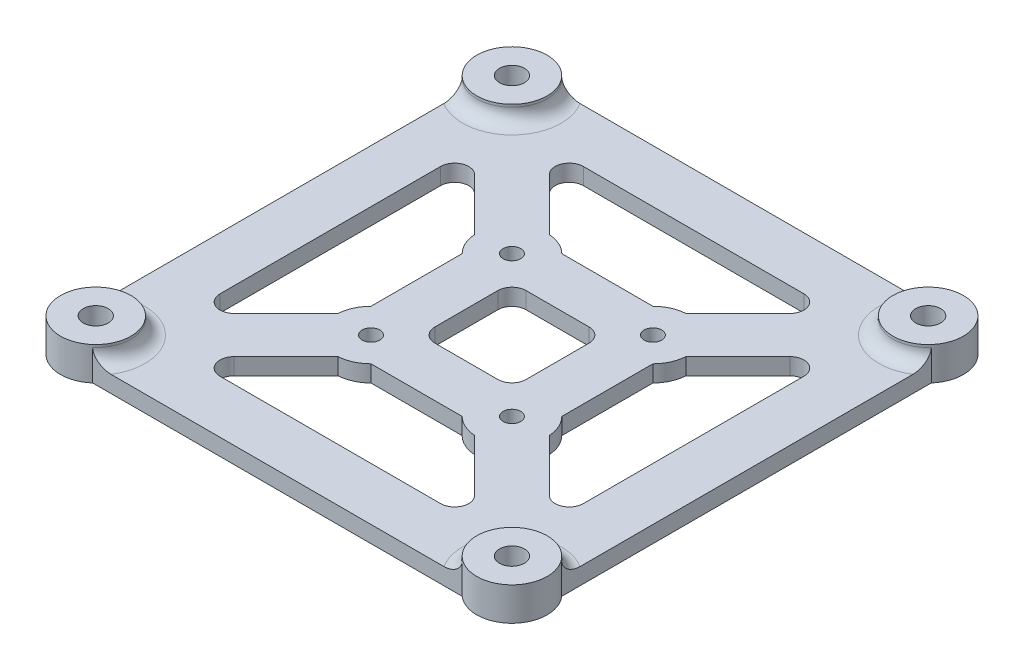
SolidWorks part; units mm, degrees
ref_plane "Front Plane" through (0, 0, 0) normal (0, 0, 1) x (1, 0, 0)
ref_plane "Top Plane" through (0, 0, 0) normal (0, 1, 0) x (1, 0, 0)
ref_plane "Right Plane" through (0, 0, 0) normal (1, 0, 0) x (0, 0, -1)
sketch "Sketch1" plane through (0, 0, 0) normal (0, 1, 0) x (1, 0, 0)
  line L0 (-26.0023, -32.7375) -> (-12.3023, -19.0375)
  line L1 (-12.7, -12.7) -> (12.7, -12.7) construction
  line L2 (-12.7, -12.7) -> (-12.7, 12.7) construction
  line L3 (-12.7, 12.7) -> (12.7, 12.7) construction
  line L4 (12.7, -12.7) -> (12.7, 12.7) construction
  line L5 (-12.7, -12.7) -> (12.7, 12.7) construction
  line L6 (-12.7, 12.7) -> (12.7, -12.7) construction
  line L7 (-37.5, -37.5) -> (37.5, -37.5) construction
  line L8 (-37.5, -37.5) -> (-37.5, 37.5) construction
  line L9 (-37.5, 37.5) -> (37.5, 37.5) construction
  line L10 (37.5, -37.5) -> (37.5, 37.5) construction
  line L11 (-37.5, -37.5) -> (37.5, 37.5) construction
  line L12 (-37.5, 37.5) -> (37.5, -37.5) construction
  line L13 (-33.2999, -42.2625) -> (33.2999, -42.2625)
  line L14 (-33.2999, -42.2625) -> (-33.2999, -32.7375)
  line L15 (-33.2999, -32.7375) -> (33.2999, -32.7375)
  line L16 (33.2999, -42.2625) -> (33.2999, -32.7375)
  line L17 (-33.2999, -42.2625) -> (33.2999, -32.7375) construction
  line L18 (-33.2999, -32.7375) -> (33.2999, -42.2625) construction
  line L19 (32.7375, -33.2999) -> (42.2625, -33.2999)
  line L20 (32.7375, -33.2999) -> (32.7375, 33.2999)
  line L21 (32.7375, 33.2999) -> (42.2625, 33.2999)
  line L22 (42.2625, -33.2999) -> (42.2625, 33.2999)
  line L23 (32.7375, -33.2999) -> (42.2625, 33.2999) construction
  line L24 (32.7375, 33.2999) -> (42.2625, -33.2999) construction
  line L25 (-33.2999, 32.7375) -> (33.2999, 32.7375)
  line L26 (-33.2999, 32.7375) -> (-33.2999, 42.2625)
  line L27 (-33.2999, 42.2625) -> (33.2999, 42.2625)
  line L28 (33.2999, 32.7375) -> (33.2999, 42.2625)
  line L29 (-33.2999, 32.7375) -> (33.2999, 42.2625) construction
  line L30 (-33.2999, 42.2625) -> (33.2999, 32.7375) construction
  line L31 (-42.2625, -33.2999) -> (-32.7375, -33.2999)
  line L32 (-42.2625, -33.2999) -> (-42.2625, 33.2999)
  line L33 (-42.2625, 33.2999) -> (-32.7375, 33.2999)
  line L34 (-32.7375, -33.2999) -> (-32.7375, 33.2999)
  line L35 (-42.2625, -33.2999) -> (-32.7375, 33.2999) construction
  line L36 (-42.2625, 33.2999) -> (-32.7375, -33.2999) construction
  line L41 (-8.2099, -8.2099) -> (8.2099, -8.2099)
  line L42 (-8.2099, -8.2099) -> (-8.2099, 8.2099)
  line L47 (-8.2099, 8.2099) -> (8.2099, 8.2099)
  line L48 (8.2099, -8.2099) -> (8.2099, 8.2099)
  line L53 (-8.2099, -8.2099) -> (8.2099, 8.2099) construction
  line L54 (-8.2099, 8.2099) -> (8.2099, -8.2099) construction
  line L59 (-17.1901, -8.2099) -> (17.1901, -8.2099)
  line L60 (-17.1901, -8.2099) -> (-17.1901, 8.2099)
  line L61 (-17.1901, 8.2099) -> (17.1901, 8.2099)
  line L62 (17.1901, -8.2099) -> (17.1901, 8.2099)
  line L63 (-17.1901, -8.2099) -> (17.1901, 8.2099) construction
  line L64 (-17.1901, 8.2099) -> (17.1901, -8.2099) construction
  line L65 (-8.2099, -17.1901) -> (8.2099, -17.1901)
  line L66 (-8.2099, -17.1901) -> (-8.2099, 17.1901)
  line L67 (-8.2099, 17.1901) -> (8.2099, 17.1901)
  line L68 (8.2099, -17.1901) -> (8.2099, 17.1901)
  line L69 (-8.2099, -17.1901) -> (8.2099, 17.1901) construction
  line L70 (-8.2099, 17.1901) -> (8.2099, -17.1901) construction
  line L71 (-19.0375, -12.3023) -> (-32.7375, -26.0023)
  line L72 (12.3023, -19.0375) -> (26.0023, -32.7375)
  line L73 (19.0375, -12.3023) -> (32.7375, -26.0023)
  line L74 (-12.3023, 19.0375) -> (-26.0023, 32.7375)
  line L75 (-19.0375, 12.3023) -> (-32.7375, 26.0023)
  line L76 (12.3023, 19.0375) -> (26.0023, 32.7375)
  line L77 (19.0375, 12.3023) -> (32.7375, 26.0023)
  circle A4 centre (12.7, 12.7) radius 6.35
  circle A5 centre (12.7, -12.7) radius 6.35
  circle A6 centre (-12.7, -12.7) radius 6.35
  circle A7 centre (-12.7, 12.7) radius 6.35
  circle A8 centre (-37.5, -37.5) radius 6.35
  circle A9 centre (37.5, -37.5) radius 6.35
  circle A10 centre (37.5, 37.5) radius 6.35
  circle A11 centre (-37.5, 37.5) radius 6.35
  point P0 (0, 0)
  point P5 (0, 0)
  point P19 (0, -37.5)
  point P24 (37.5, 0)
  point P29 (0, 37.5)
  point P34 (-37.5, 0)
  point P39 (-12.7, 0)
  point P40 (0, 0)
  point P44 (0, 12.7)
  point P46 (0, 0)
  point P49 (12.7, 0)
  point P52 (0, 0)
  point P53 (0, -12.7)
  dimension "D5" = 12.7
  dimension "D6" = 12.7
  dimension "D7" = 12.7
  dimension "D8" = 12.7
  dimension "D9" = 12.7
  dimension "D10" = 12.7
  dimension "D11" = 12.7
  dimension "D12" = 12.7
  dimension "D2" = 25.4
  dimension "D3" = 75
  dimension "D4" = 75
  dimension "D13" = 9.525
  dimension "D14" = 9.525
  dimension "D15" = 9.525
  dimension "D16" = 9.525
  dimension "D17" = 9.525
  dimension "D18" = 4.7625
  dimension "D19" = 4.7625
  dimension "D20" = 9.525
  dimension "D21" = 4.7625
  dimension "D22" = 9.525
  dimension "D23" = 4.7625
  dimension "D24" = 9.525
extrude "Boss-Extrude1" add sketch "Sketch1" along normal blind 3 contours L31 A8 L14 | L14 A8 L31 | A9 L20 L15 L34 A8 L13 | A6 L71 L34 L15 L0 | A11 L32 A8 L15 L34 L25 | L14 A8 L31 | A6 L66 L59 | A6 L65 A5 L41 | L66 A6 | L59 A6 | A7 L60 A6 L42 | L68 A5 | A5 L59 L68 | L59 A5 | A5 L72 L15 L20 L73 | L16 A9 L19 | L19 A9 L16 | L16 A9 L19 | A9 L15 L20 | L19 A9 L16 | A10 L25 L20 L15 A9 L22 | L31 A8 L14 | A8 L34 L15 | L61 A7 | L66 A7 L61 | L66 A7 | A7 L47 A4 L67 | L68 A4 | L61 A4 L68 | L61 A4 | A5 L62 A4 L48 | A4 L77 L20 L25 L76 | A7 L74 L25 L34 L75 | L28 A10 L21 | L21 A10 L28 | L28 A10 L21 | L21 A10 L28 | A10 L20 L25 | A11 L34 L25 L20 A10 L27 | L33 A11 L26 | L26 A11 L33 | L33 A11 L26 | L26 A11 L33 | A11 L25 L34 region at (-23.9149, 0, 23.9149) region at (0, 0, 37.5023) region at (-13.2822, 0, 13.2822) region at (23.9149, 0, 23.9149) region at (-32.921, 0, 32.921) region at (-37.5023, 0, 0) region at (0, 0, 12.7) region at (-7.4557, 0, 12.7) region at (37.5023, 0, 0) region at (32.921, 0, 32.921) region at (13.2822, 0, 13.2822) region at (-33.1085, 0, 33.1085) region at (-37.5516, 0, 32.4181) region at (-32.4181, 0, 37.5516) region at (-12.7, 0, 7.4557) region at (-12.7, 0, 0) region at (7.4557, 0, 12.7) region at (37.5516, 0, 32.4181) region at (33.1085, 0, 33.1085) region at (32.4181, 0, 37.5516) region at (-38.2241, 0, 38.2241) region at (-23.9149, 0, -23.9149) region at (-13.2822, 0, -13.2822) region at (-12.7, 0, -7.4557) region at (12.7, 0, 7.4557) region at (12.7, 0, 0) region at (0, 0, -12.7) region at (-7.4557, 0, -12.7) region at (38.2241, 0, 38.2241) region at (23.9149, 0, -23.9149) region at (-38.2241, 0, -38.2241) region at (-37.5516, 0, -32.4181) region at (0, 0, -37.5023) region at (-32.921, 0, -32.921) region at (13.2822, 0, -13.2822) region at (7.4557, 0, -12.7) region at (12.7, 0, -7.4557) region at (37.5516, 0, -32.4181) region at (38.2241, 0, -38.2241) region at (32.921, 0, -32.921) region at (-33.1085, 0, -33.1085) region at (-32.4181, 0, -37.5516) region at (33.1085, 0, -33.1085) region at (32.4181, 0, -37.5516)
sketch "Sketch2" plane through (0, 3, 0) normal (0, 1, 0) x (1, 0, 0)
  circle A0 centre (-37.5, 37.5) radius 6.35
  circle A1 centre (37.5, 37.5) radius 6.35
  circle A2 centre (37.5, -37.5) radius 6.35
  circle A3 centre (-37.5, -37.5) radius 6.35
extrude "Boss-Extrude2" add sketch "Sketch2" along normal blind 3
sketch "Sketch3" plane through (0, 3, 0) normal (0, 1, 0) x (1, 0, 0)
  circle A0 centre (-12.7, 12.7) radius 1.5875
  circle A1 centre (12.7, 12.7) radius 1.5875
  circle A2 centre (12.7, -12.7) radius 1.5875
  circle A3 centre (-12.7, -12.7) radius 1.5875
  dimension "D1" = 3.175
  dimension "D2" = 3.175
  dimension "D3" = 3.175
  dimension "D4" = 3.175
extrude "Cut-Extrude1" cut sketch "Sketch3" against normal through all
fillet "Fillet1" radius 2.54 12 edges at (-8.2099, 1.5, 8.2099) (8.2099, 1.5, 8.2099) (8.2099, 1.5, -8.2099) (-8.2099, 1.5, -8.2099) (-32.7375, 1.5, -26.0023) (-32.7375, 1.5, 26.0023) (-26.0023, 1.5, 32.7375) (26.0023, 1.5, 32.7375) (32.7375, 1.5, 26.0023) (32.7375, 1.5, -26.0023) (26.0023, 1.5, -32.7375) (-26.0023, 1.5, -32.7375)
sketch "Sketch4" plane through (0, 6, 0) normal (0, 1, 0) x (1, 0, 0)
  circle A0 centre (-37.5, 37.5) radius 2.25
  dimension "D1" = 4.5
extrude "Cut-Extrude2" cut sketch "Sketch4" against normal through all
mirror "Mirror1" about plane through (0, 0, 0) normal (1, 0, 0) of "Cut-Extrude2" second plane through (0, 0, 0) second plane normal (0, 0, 1)
fillet "Fillet2" radius 2.54 4 edges at (33.0099, 3, 33.0099) (-33.0099, 3, 33.0099) (-33.0099, 3, -33.0099) (33.0099, 3, -33.0099)
